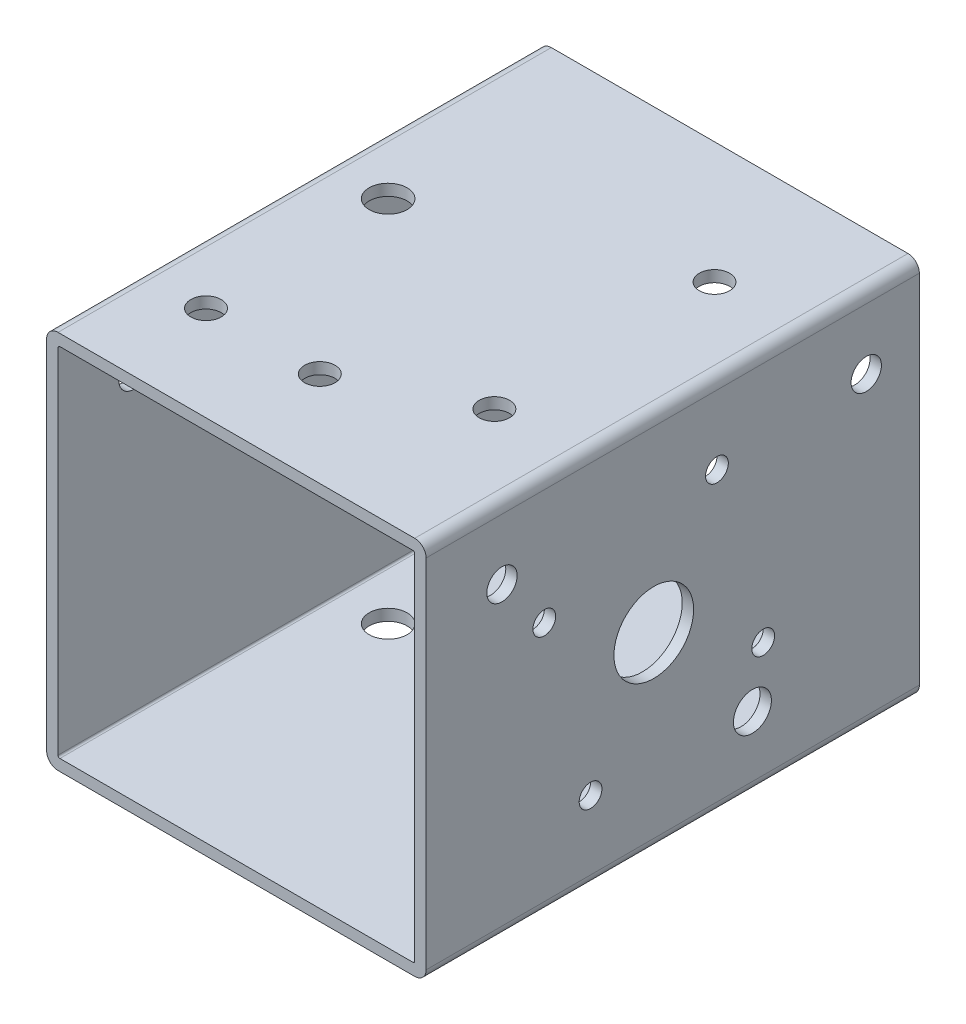
SolidWorks part; units mm, degrees
ref_plane "Front Plane" through (0, 0, 0) normal (0, 0, 1) x (1, 0, 0)
ref_plane "Top Plane" through (0, 0, 0) normal (0, 1, 0) x (1, 0, 0)
ref_plane "Right Plane" through (0, 0, 0) normal (1, 0, 0) x (0, 0, -1)
sketch "Sketch1" plane through (0, 0, 0) normal (0, 0, 1) x (1, 0, 0)
  line L1 (-50, 50) -> (50, 50)
  line L2 (-50, 50) -> (-50, -50)
  line L3 (-50, -50) -> (50, -50)
  line L4 (50, 50) -> (50, -50)
  line L5 (-50, 50) -> (50, -50) construction
  line L6 (-50, -50) -> (50, 50) construction
  point P0 (0, 0)
  dimension "D1" = 100
  dimension "D2" = 100
extrude "Extrude-Thin1" add sketch "Sketch1" along normal blind 130 thin thin type one direction reverse wall 3
fillet "Fillet1" radius 0.5 4 edges at (-47, -47, 65) (-47, 47, 65) (47, 47, 65) (47, -47, 65)
fillet "Fillet2" radius 3 4 edges at (50, -50, 65) (-50, -50, 65) (50, 50, 65) (-50, 50, 65)
sketch "Holes - top" plane through (0, 0, 0) normal (0, 1, 0) x (1, 0, 0)
  line L0 (-3, 0) -> (-3, -130) construction
  line L1 (47, -130) -> (-47, -130) construction
  line L2 (-23, 0) -> (-23, -130) construction
  line L3 (47, 0) -> (-47, 0) construction
  line L4 (17, 0) -> (17, -130) construction
  circle A0 centre (-34, -56) radius 11 construction
  circle A1 centre (28, -90) radius 11 construction
  circle A2 centre (28, -32) radius 11 construction
  dimension "D4" = 22
  dimension "D1" = 40
  dimension "D2" = 40
  dimension "D3" = 32
  dimension "D5" = 56
  dimension "D6" = 3
hole_wizard "Ø8.0 (8) Diameter Hole2" positions "Sketch6" profile "Sketch5" hole size "Ø8.0" standard "ANSI Metric" end condition through all
sketch "Sketch6" plane through (0, 50, 0) normal (0, 1, 0) x (1, 0, 0)
  point P0 (28, -32)
  point P6 (28, -90)
sketch "Sketch5" plane through (28, 50, 32) normal (1, 0, 0) x (0, 0, 1)
  line L0 (0, 0) -> (0, 100)
  line L1 (0, 100) -> (4, 100)
  line L2 (4, 100) -> (4, 0)
  line L5 (4, 0) -> (0, 0)
  line L11 (0, -6.35) -> (0, 107.95) construction
  dimension "Thru Hole Dia." = 8
  dimension "Thru Hole Depth" = 100
sketch "Holes - side" plane through (0, 0, 0) normal (1, 0, 0) x (0, 0, -1)
  line L0 (0, 0) -> (-130, 0) construction
  line L1 (-130, -47) -> (-130, 47) construction
  line L2 (-130, 20) -> (0, 20) construction
  line L3 (0, -47) -> (0, 47) construction
  line L4 (-130, -20) -> (0, -20) construction
  circle A0 centre (-110, 31) radius 11 construction
  circle A1 centre (-14, 31) radius 11 construction
  circle A2 centre (-44, -31) radius 11 construction
  dimension "D1" = 40
  dimension "D2" = 22
  dimension "D3" = 20
  dimension "D4" = 14
  dimension "D5" = 44
hole_wizard "Ø8.0 (8) Diameter Hole3" positions "Sketch9" profile "Sketch8" hole size "Ø8.0" standard "ANSI Metric" end condition through all
sketch "Sketch9" plane through (50, 0, 0) normal (1, 0, 0) x (0, 0, -1)
  point P0 (-14, 31)
  point P3 (-110, 31)
sketch "Sketch8" plane through (50, 31, 14) normal (0, 1, 0) x (0, 0, -1)
  line L0 (0, 0) -> (0, 100)
  line L1 (0, 100) -> (4, 100)
  line L2 (4, 100) -> (4, 0)
  line L5 (4, 0) -> (0, 0)
  line L11 (0, -6.35) -> (0, 107.95) construction
  dimension "Thru Hole Dia." = 8
  dimension "Thru Hole Depth" = 100
hole_wizard "Ø10.0 (10) Diameter Hole1" positions "Sketch12" profile "Sketch11" hole size "Ø10.0" standard "ANSI Metric" end condition through all
sketch "Sketch12" plane through (0, 50, 0) normal (0, 1, 0) x (1, 0, 0)
  point P0 (-34, -56)
sketch "Sketch11" plane through (-34, 50, 56) normal (1, 0, 0) x (0, 0, 1)
  line L0 (0, 0) -> (0, 100)
  line L1 (0, 100) -> (5, 100)
  line L2 (5, 100) -> (5, 0)
  line L5 (5, 0) -> (0, 0)
  line L11 (0, -6.35) -> (0, 107.95) construction
  dimension "Thru Hole Dia." = 10
  dimension "Thru Hole Depth" = 100
hole_wizard "Ø10.0 (10) Diameter Hole2" positions "Sketch14" profile "Sketch13" hole size "Ø10.0" standard "ANSI Metric" end condition through all
sketch "Sketch14" plane through (50, 0, 0) normal (1, 0, 0) x (0, 0, -1)
  point P0 (-44, -31)
sketch "Sketch13" plane through (50, -31, 44) normal (0, 1, 0) x (0, 0, -1)
  line L0 (0, 0) -> (0, 100)
  line L1 (0, 100) -> (5, 100)
  line L2 (5, 100) -> (5, 0)
  line L5 (5, 0) -> (0, 0)
  line L11 (0, -6.35) -> (0, 107.95) construction
  dimension "Thru Hole Dia." = 10
  dimension "Thru Hole Depth" = 100
hole_wizard "M8x1.25 Tapped Hole1" positions "Sketch18" profile "Sketch17" tap size "M8x1.25" standard "ANSI Metric" end condition up to next
sketch "Sketch18" plane through (-50, 0, 0) normal (-1, 0, 0) x (0, 0, 1)
  line L0 (56, 35) -> (56, -15) construction
  point P0 (56, -15)
  point P2 (56, 35)
  dimension "D1" = 56
  dimension "D2" = 35
  dimension "D3" = 15
sketch "Sketch17" plane through (-50, -15, 56) normal (0, 1, 0) x (0, 0, 1)
  line L0 (0, 0) -> (0, 3)
  line L1 (0, 3) -> (3.4, 3)
  line L2 (3.4, 3) -> (3.4, 0)
  line L5 (3.4, 0) -> (0, 0)
  line L11 (0, -6.35) -> (0, 107.95) construction
  dimension "Thru Tap Drill Dia." = 6.8
  dimension "Thru Tap Drill Depth" = 3
cosmetic thread "Hole Thread1" parameters "D2"=8
cosmetic thread "Hole Thread2" parameters "D2"=8
hole_wizard "M8x1.25 Tapped Hole2" positions "Sketch21" profile "Sketch20" tap size "M8x1.25" standard "ANSI Metric" end condition up to next
sketch "Sketch21" plane through (0, -50, 0) normal (0, -1, 0) x (-1, 0, 0)
  line L0 (20, -44) -> (-35, -44) construction
  point P0 (20, -44)
  point P2 (-35, -44)
  dimension "D1" = 44
  dimension "D2" = 35
  dimension "D3" = 20
sketch "Sketch20" plane through (-20, -50, 44) normal (1, 0, 0) x (0, 0, -1)
  line L0 (0, 0) -> (0, 3)
  line L1 (0, 3) -> (3.4, 3)
  line L2 (3.4, 3) -> (3.4, 0)
  line L5 (3.4, 0) -> (0, 0)
  line L11 (0, -6.35) -> (0, 107.95) construction
  dimension "Thru Tap Drill Dia." = 6.8
  dimension "Thru Tap Drill Depth" = 3
cosmetic thread "Hole Thread3" parameters "D2"=8
cosmetic thread "Hole Thread4" parameters "D2"=8
sketch "Holes - Nema 23 motor" plane through (0, 0, 0) normal (1, 0, 0) x (0, 0, -1)
  line L0 (-98.8427, 16.6524) -> (-53.3476, 28.8427) construction
  line L1 (-98.8427, 16.6524) -> (-86.6524, -28.8427) construction
  line L2 (-53.3476, 28.8427) -> (-41.1573, -16.6524) construction
  line L3 (-86.6524, -28.8427) -> (-41.1573, -16.6524) construction
  line L4 (-98.8427, 16.6524) -> (-41.1573, -16.6524) construction
  line L5 (-53.3476, 28.8427) -> (-86.6524, -28.8427) construction
  line L6 (0, 0) -> (-130, 0) construction
  point P1 (-70, 0)
  dimension "D1" = 70
  dimension "D2" = 47.1
  dimension "D3" = 47.1
  dimension "D4" = 15
hole_wizard "Ø21.0 (21) Diameter Hole1" positions "Sketch24" profile "Sketch23" hole size "Ø21.0" standard "ANSI Metric" end condition up to next
sketch "Sketch24" plane through (50, 0, 0) normal (1, 0, 0) x (0, 0, -1)
  point P0 (-70, 0)
sketch "Sketch23" plane through (50, 0, 70) normal (0, 1, 0) x (0, 0, -1)
  line L0 (0, 0) -> (0, 3)
  line L1 (0, 3) -> (10.5, 3)
  line L2 (10.5, 3) -> (10.5, 0)
  line L5 (10.5, 0) -> (0, 0)
  line L11 (0, -6.35) -> (0, 107.95) construction
  dimension "Thru Hole Dia." = 21
  dimension "Thru Hole Depth" = 3
hole_wizard "Ø6.0 (6) Diameter Hole1" positions "Sketch26" profile "Sketch25" hole size "Ø6.0" standard "ANSI Metric" end condition up to next
sketch "Sketch26" plane through (50, 0, 0) normal (1, 0, 0) x (0, 0, -1)
  point P0 (-41.1573, -16.6524)
  point P3 (-53.3476, 28.8427)
  point P6 (-98.8427, 16.6524)
  point P9 (-86.6524, -28.8427)
sketch "Sketch25" plane through (50, -16.6524, 41.1573) normal (0, 1, 0) x (0, 0, -1)
  line L0 (0, 0) -> (0, 3)
  line L1 (0, 3) -> (3, 3)
  line L2 (3, 3) -> (3, 0)
  line L5 (3, 0) -> (0, 0)
  line L11 (0, -6.35) -> (0, 107.95) construction
  dimension "Thru Hole Dia." = 6
  dimension "Thru Hole Depth" = 3
hole_wizard "Ø8.0 (8) Diameter Hole4" positions "Sketch29" profile "Sketch28" hole size "Ø8.0" standard "ANSI Metric" end condition up to next
sketch "Sketch29" plane through (0, 50, 0) normal (0, 1, 0) x (1, 0, 0)
  line L0 (-3, 0) -> (-3, -130) construction
  point P0 (-3, -105)
  dimension "D1" = 15
sketch "Sketch28" plane through (-3, 50, 105) normal (1, 0, 0) x (0, 0, 1)
  line L0 (0, 0) -> (0, 3)
  line L1 (0, 3) -> (4, 3)
  line L2 (4, 3) -> (4, 0)
  line L5 (4, 0) -> (0, 0)
  line L11 (0, -6.35) -> (0, 107.95) construction
  dimension "Thru Hole Dia." = 8
  dimension "Thru Hole Depth" = 3
sketch "Sketch32" plane through (50, 0, 0) normal (1, 0, 0) x (0, 0, -1)
  line L1 (0, -47) -> (0, 47) construction
  line L2 (-65, 69.5535) -> (-65, -72.7704) construction
  line L3 (-130, -47) -> (-130, 47) construction
  line L4 (-130, 50) -> (0, 50) construction
  circle A0 centre (-5, 13) radius 2
  circle A1 centre (-5, 4) radius 2
  circle A2 centre (-125, 4) radius 2
  circle A3 centre (-125, 13) radius 2
  dimension "D1" = 46
  dimension "D2" = 9
  dimension "D3" = 4
  dimension "D5" = 5
  dimension "D4" = 0
  dimension "D6" = 65
sketch "Sketch33" plane through (0, 50, 0) normal (0, 1, 0) x (1, 0, 0)
  line L0 (47, -130) -> (-47, -130) construction
  circle A0 centre (-33, -105) radius 4
  circle A2 centre (-3, -105) radius 4 construction
  dimension "D3" = 8
  dimension "D1" = 25
  dimension "D2" = 30
extrude "Cut-Extrude1" cut sketch "Sketch33" against normal blind 10
equation "\"a\"= \"Trolley Profile@Plasma Beta.SLDASM\""
equation "\"b\"= \"Trolley Profile Thickness@Plasma Beta.SLDASM\""
equation "\"L\"= 130"
equation "\"D2@Sketch1\"=\"a\""
equation "\"D1@Sketch1\"=\"a\""
equation "\"D1@Extrude-Thin1\"=\"L\""
equation "\"D5@Extrude-Thin1\"=\"b\""
equation "\"D1@Fillet2\"=\"b\""
equation "\"d-bearing\"= 22'diameter of bearing"
equation "\"a-small\"= \"Beam Profile@Plasma Beta.SLDASM\"'profile of smaller beam"
equation "\"D4@Holes - top\"=\"d-bearing\""
equation "\"D2@Holes - side\"=\"d-bearing\""
equation "\"D1@Holes - top\"=\"a-small\""
equation "\"D1@Holes - side\"=\"a-small\""
